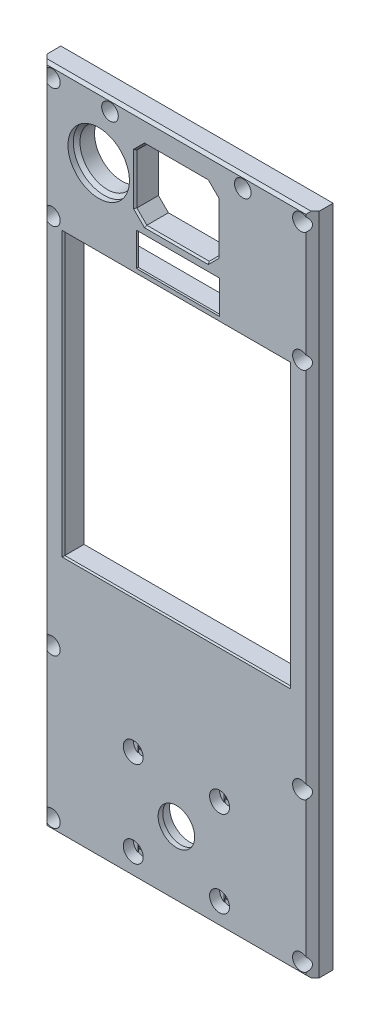
SolidWorks part; units mm, degrees
ref_plane "Front Plane" through (0, 0, 0) normal (0, 0, 1) x (1, 0, 0)
ref_plane "Top Plane" through (0, 0, 0) normal (0, 1, 0) x (1, 0, 0)
ref_plane "Right Plane" through (0, 0, 0) normal (1, 0, 0) x (0, 0, -1)
sketch "Sketch1" plane through (0, 0, 0) normal (0, 0, 1) x (1, 0, 0)
  line L1 (-41, -100) -> (41, -100)
  line L2 (-41, -100) -> (-41, 100)
  line L3 (-41, 100) -> (41, 100)
  line L4 (41, -100) -> (41, 100)
  line L5 (-41, -100) -> (41, 100) construction
  line L6 (-41, 100) -> (41, -100) construction
  line L7 (-34, -93) -> (34, -93)
  line L8 (-34, -93) -> (-34, 93)
  line L9 (-34, 93) -> (34, 93)
  line L10 (34, -93) -> (34, 93)
  line L11 (-34, -93) -> (34, 93) construction
  line L12 (-34, 93) -> (34, -93) construction
  point P0 (0, 0)
  point P6 (0, 0)
  dimension "D1" = 200
  dimension "D2" = 82
  dimension "D3" = 7
  dimension "D4" = 7
extrude "Boss-Extrude1" add sketch "Sketch1" along normal blind 7
sketch "Sketch2" plane through (0, 0, 7) normal (0, 0, 1) x (1, 0, 0)
  line L0 (34, -93) -> (34, 93) construction
  line L1 (-34, -93) -> (34, -93)
  line L2 (-34, -93) -> (-34, -57)
  line L3 (-34, -57) -> (34, -57)
  line L4 (34, -93) -> (34, -57)
  dimension "D1" = 36
extrude "Boss-Extrude2" add sketch "Sketch2" against normal up to surface (7 mm away) up to face at (0, 0, 0)
sketch "Sketch3" plane through (0, 0, 0) normal (0, 0, -1) x (-1, 0, 0)
  line L0 (0, -100) -> (0, -80) construction
  line L1 (41, -100) -> (-41, -100) construction
  circle A0 centre (0, -80) radius 5.5
  dimension "D1" = 11
  dimension "D2" = 20
extrude "Cut-Extrude1" cut sketch "Sketch3" against normal through all
sketch "Sketch4" plane through (0, 0, 0) normal (0, 0, -1) x (-1, 0, 0)
  circle A0 centre (0, -80) radius 6.05
  dimension "D1" = 12.1
extrude "Cut-Extrude2" cut sketch "Sketch4" against normal offset from surface (5.6 mm away) 1.4 up to face at (-5.5, -80, 7)
sketch "Sketch5" plane through (0, 0, 0) normal (0, 0, -1) x (-1, 0, 0)
  circle A0 centre (0, -80) radius 11.1
  dimension "D1" = 22.2
extrude "Cut-Extrude3" cut sketch "Sketch5" against normal offset from surface (3 mm away) 2.6 up to face at (-6.05, -80, 5.6)
sketch "Sketch6" plane through (0, 0, 0) normal (0, 0, -1) x (-1, 0, 0)
  line L1 (-13, -93) -> (13, -93) construction
  line L2 (-13, -93) -> (-13, -67) construction
  line L3 (-13, -67) -> (13, -67) construction
  line L4 (13, -93) -> (13, -67) construction
  line L5 (-13, -93) -> (13, -67) construction
  line L6 (-13, -67) -> (13, -93) construction
  circle A0 centre (-13, -67) radius 1.6
  circle A1 centre (13, -67) radius 1.6
  circle A2 centre (13, -93) radius 1.6
  circle A3 centre (-13, -93) radius 1.6
  point P0 (0, -80)
  dimension "D2" = 3.2
  dimension "D1" = 26
extrude "Cut-Extrude4" cut sketch "Sketch6" against normal through all
sketch "Sketch7" plane through (0, 0, 0) normal (0, 0, -1) x (-1, 0, 0)
  line L1 (-25, -99) -> (25, -99)
  line L2 (-25, -99) -> (-25, -61)
  line L3 (-25, -61) -> (25, -61)
  line L4 (25, -99) -> (25, -61)
  line L5 (-25, -99) -> (25, -61) construction
  line L6 (-25, -61) -> (25, -99) construction
  point P0 (0, -80)
  dimension "D1" = 50
  dimension "D2" = 38
extrude "Cut-Extrude5" cut sketch "Sketch7" against normal blind 1
sketch "Sketch8" plane through (0, 0, 7) normal (0, 0, 1) x (1, 0, 0)
  circle A0 centre (-13, -67) radius 3
  circle A1 centre (13, -67) radius 3
  circle A2 centre (13, -93) radius 3
  circle A3 centre (-13, -93) radius 3
  dimension "D1" = 6
extrude "Cut-Extrude6" cut sketch "Sketch8" against normal blind 3
sketch "Sketch9" plane through (0, 0, 7) normal (0, 0, 1) x (1, 0, 0)
  line L0 (-41, 100) -> (-41, -100) construction
  line L1 (-37.5, -96.5) -> (37.5, -96.5) construction
  line L2 (-37.5, -96.5) -> (-37.5, 96.5) construction
  line L3 (-37.5, 96.5) -> (37.5, 96.5) construction
  line L4 (37.5, -96.5) -> (37.5, 96.5) construction
  line L5 (-37.5, -96.5) -> (37.5, 96.5) construction
  line L6 (-37.5, 96.5) -> (37.5, -96.5) construction
  line L7 (41, 100) -> (-41, 100) construction
  circle A0 centre (-37.5, 96.5) radius 1.35
  circle A1 centre (37.5, 96.5) radius 1.35
  circle A2 centre (37.5, -96.5) radius 1.35
  circle A3 centre (-37.5, -96.5) radius 1.35
  circle A6 centre (-37.5, 60.5) radius 1.35
  circle A7 centre (-37.5, -51.5) radius 1.35
  circle A8 centre (37.5, -51.5) radius 1.35
  circle A9 centre (37.5, 60.5) radius 1.35
  point P0 (0, 0)
  dimension "D3" = 2.7
  dimension "D4" = 45
  dimension "D5" = 36
  dimension "D1" = 3.5
  dimension "D2" = 3.5
extrude "Cut-Extrude7" cut sketch "Sketch9" against normal through all
sketch "Sketch10" plane through (0, 0, 7) normal (0, 0, 1) x (1, 0, 0)
  circle A0 centre (-37.5, 96.5) radius 2.5
  circle A1 centre (37.5, 96.5) radius 2.5
  circle A2 centre (-37.5, 60.5) radius 2.5
  circle A3 centre (-37.5, -51.5) radius 2.5
  circle A4 centre (-37.5, -96.5) radius 2.5
  circle A5 centre (37.5, -96.5) radius 2.5
  circle A6 centre (37.5, 60.5) radius 2.5
  circle A7 centre (37.5, -51.5) radius 2.5
  dimension "D1" = 5
extrude "Cut-Extrude8" cut sketch "Sketch10" against normal blind 5
chamfer "Chamfer1" distance 2 angle 45 2 edges at (-41, 0, 7) (41, 0, 7)
sketch "Sketch11" plane through (0, 0, 7) normal (0, 0, 1) x (1, 0, 0)
  line L0 (34, -57) -> (34, 93) construction
  line L1 (-34, -57) -> (34, -57)
  line L2 (-34, -57) -> (-34, -26.5)
  line L3 (-34, -26.5) -> (34, -26.5)
  line L4 (34, -57) -> (34, -26.5)
  line L5 (-39, -100) -> (39, -100) construction
  dimension "D1" = 73.5
extrude "Boss-Extrude3" add sketch "Sketch11" against normal up to surface (7 mm away) up to face at (38.85, 96.5, 0)
sketch "Sketch12" plane through (0, 0, 2) normal (0, 0, 1) x (1, 0, 0)
  line L2 (-38.85, -98.6042) -> (-38.85, -94.3958)
  line L4 (-36.15, -98.6042) -> (-36.15, -94.3958)
  line L5 (-38.85, -98.6042) -> (-36.15, -94.3958) construction
  line L6 (-38.85, -94.3958) -> (-36.15, -98.6042) construction
  line L8 (-38.85, -53.6042) -> (-38.85, -49.3958)
  line L10 (-36.15, -53.6042) -> (-36.15, -49.3958)
  line L11 (-38.85, -53.6042) -> (-36.15, -49.3958) construction
  line L12 (-38.85, -49.3958) -> (-36.15, -53.6042) construction
  line L14 (-38.85, 58.3958) -> (-38.85, 62.6042)
  line L16 (-36.15, 58.3958) -> (-36.15, 62.6042)
  line L17 (-38.85, 58.3958) -> (-36.15, 62.6042) construction
  line L18 (-38.85, 62.6042) -> (-36.15, 58.3958) construction
  line L20 (-38.85, 94.3958) -> (-38.85, 98.6042)
  line L22 (-36.15, 94.3958) -> (-36.15, 98.6042)
  line L23 (-38.85, 94.3958) -> (-36.15, 98.6042) construction
  line L24 (-38.85, 98.6042) -> (-36.15, 94.3958) construction
  arc A0 (-39, -98.5) -> (-39, -94.5) centre (-37.5, -96.5) ccw construction
  circle A1 centre (-37.5, -51.5) radius 2.5 construction
  circle A2 centre (-37.5, 60.5) radius 2.5 construction
  arc A3 (-39, 94.5) -> (-39, 98.5) centre (-37.5, 96.5) ccw construction
  circle A4 centre (-37.5, 96.5) radius 1.35 construction
  circle A5 centre (-37.5, 96.5) radius 2.5 construction
  arc A6 (-36.15, 98.6042) -> (-38.85, 98.6042) centre (-37.5, 96.5) ccw
  arc A7 (-38.85, 94.3958) -> (-36.15, 94.3958) centre (-37.5, 96.5) ccw
  circle A8 centre (-37.5, 60.5) radius 1.35 construction
  arc A9 (-38.85, 58.3958) -> (-36.15, 58.3958) centre (-37.5, 60.5) ccw
  arc A10 (-36.15, 62.6042) -> (-38.85, 62.6042) centre (-37.5, 60.5) ccw
  circle A11 centre (-37.5, -51.5) radius 1.35 construction
  arc A12 (-38.85, -53.6042) -> (-36.15, -53.6042) centre (-37.5, -51.5) ccw
  arc A13 (-36.15, -49.3958) -> (-38.85, -49.3958) centre (-37.5, -51.5) ccw
  circle A14 centre (-37.5, -96.5) radius 1.35 construction
  arc A16 (-38.85, -98.6042) -> (-36.15, -98.6042) centre (-37.5, -96.5) ccw
  arc A18 (-36.15, -94.3958) -> (-38.85, -94.3958) centre (-37.5, -96.5) ccw
  point P0 (-37.5, -96.5)
  point P9 (-37.5, -51.5)
  point P17 (-37.5, 60.5)
  point P25 (-37.5, 96.5)
extrude "Cut-Extrude9" cut sketch "Sketch12" against normal blind 0.2
sketch "Sketch13" plane through (0, 0, 1.8) normal (0, 0, 1) x (1, 0, 0)
  line L0 (-36.15, -96.5) -> (-36.15, -94.3958) construction
  line L1 (-38.85, -97.85) -> (-36.15, -97.85)
  line L2 (-38.85, -97.85) -> (-38.85, -95.15)
  line L3 (-38.85, -95.15) -> (-36.15, -95.15)
  line L4 (-36.15, -97.85) -> (-36.15, -95.15)
  line L5 (-38.85, -97.85) -> (-36.15, -95.15) construction
  line L6 (-38.85, -95.15) -> (-36.15, -97.85) construction
  line L7 (-36.15, -51.5) -> (-36.15, -49.3958) construction
  line L8 (-38.85, -52.85) -> (-36.15, -52.85)
  line L9 (-38.85, -52.85) -> (-38.85, -50.15)
  line L10 (-38.85, -50.15) -> (-36.15, -50.15)
  line L11 (-36.15, -52.85) -> (-36.15, -50.15)
  line L12 (-38.85, -52.85) -> (-36.15, -50.15) construction
  line L13 (-38.85, -50.15) -> (-36.15, -52.85) construction
  line L14 (-36.15, 58.3958) -> (-36.15, 62.6042) construction
  line L15 (-38.85, 59.15) -> (-36.15, 59.15)
  line L16 (-38.85, 59.15) -> (-38.85, 61.85)
  line L17 (-38.85, 61.85) -> (-36.15, 61.85)
  line L18 (-36.15, 59.15) -> (-36.15, 61.85)
  line L19 (-38.85, 59.15) -> (-36.15, 61.85) construction
  line L20 (-38.85, 61.85) -> (-36.15, 59.15) construction
  line L21 (-36.15, 94.3958) -> (-36.15, 98.6042) construction
  line L22 (-38.85, 95.15) -> (-36.15, 95.15)
  line L23 (-38.85, 95.15) -> (-38.85, 97.85)
  line L24 (-38.85, 97.85) -> (-36.15, 97.85)
  line L25 (-36.15, 95.15) -> (-36.15, 97.85)
  line L26 (-38.85, 95.15) -> (-36.15, 97.85) construction
  line L27 (-38.85, 97.85) -> (-36.15, 95.15) construction
  arc A0 (-36.15, -96.5) -> (-38.85, -96.5) centre (-37.5, -96.5) ccw construction
  arc A1 (-36.15, -51.5) -> (-38.85, -51.5) centre (-37.5, -51.5) ccw construction
  arc A2 (-36.15, 60.5) -> (-38.85, 60.5) centre (-37.5, 60.5) ccw construction
  arc A3 (-36.15, 96.5) -> (-38.85, 96.5) centre (-37.5, 96.5) ccw construction
  point P0 (-37.5, -96.5)
  point P11 (-37.5, -51.5)
  point P22 (-37.5, 60.5)
  point P33 (-37.5, 96.5)
extrude "Cut-Extrude10" cut sketch "Sketch13" against normal blind 0.2
sketch "Sketch14" plane through (0, 0, 4) normal (0, 0, 1) x (1, 0, 0)
  line L2 (-14.6, -69.5377) -> (-14.6, -64.4623)
  line L4 (-11.4, -69.5377) -> (-11.4, -64.4623)
  line L5 (-14.6, -69.5377) -> (-11.4, -64.4623) construction
  line L6 (-14.6, -64.4623) -> (-11.4, -69.5377) construction
  line L8 (-14.6, -95.5377) -> (-14.6, -90.4623)
  line L10 (-11.4, -95.5377) -> (-11.4, -90.4623)
  line L11 (-14.6, -95.5377) -> (-11.4, -90.4623) construction
  line L12 (-14.6, -90.4623) -> (-11.4, -95.5377) construction
  circle A0 centre (-13, -67) radius 3 construction
  circle A1 centre (-13, -93) radius 3 construction
  circle A2 centre (-13, -67) radius 3 construction
  arc A3 (-14.6, -69.5377) -> (-11.4, -69.5377) centre (-13, -67) ccw
  arc A4 (-14.6, -95.5377) -> (-11.4, -95.5377) centre (-13, -93) ccw
  circle A5 centre (-13, -67) radius 1.6 construction
  circle A6 centre (-13, -93) radius 1.6 construction
  arc A7 (-11.4, -64.4623) -> (-14.6, -64.4623) centre (-13, -67) ccw
  arc A8 (-11.4, -90.4623) -> (-14.6, -90.4623) centre (-13, -93) ccw
  point P0 (-13, -67)
  point P8 (-13, -93)
extrude "Cut-Extrude11" cut sketch "Sketch14" against normal blind 0.2
sketch "Sketch15" plane through (0, 0, 3.8) normal (0, 0, 1) x (1, 0, 0)
  line L0 (-11.4, -67) -> (-11.4, -64.4623) construction
  line L1 (-14.6, -68.6) -> (-11.4, -68.6)
  line L2 (-14.6, -68.6) -> (-14.6, -65.4)
  line L3 (-14.6, -65.4) -> (-11.4, -65.4)
  line L4 (-11.4, -68.6) -> (-11.4, -65.4)
  line L5 (-14.6, -68.6) -> (-11.4, -65.4) construction
  line L6 (-14.6, -65.4) -> (-11.4, -68.6) construction
  line L7 (-11.4, -93) -> (-11.4, -90.4623) construction
  line L8 (-14.6, -94.6) -> (-11.4, -94.6)
  line L9 (-14.6, -94.6) -> (-14.6, -91.4)
  line L10 (-14.6, -91.4) -> (-11.4, -91.4)
  line L11 (-11.4, -94.6) -> (-11.4, -91.4)
  line L12 (-14.6, -94.6) -> (-11.4, -91.4) construction
  line L13 (-14.6, -91.4) -> (-11.4, -94.6) construction
  arc A0 (-11.4, -93) -> (-14.6, -93) centre (-13, -93) ccw construction
  arc A1 (-14.6, -67) -> (-11.4, -67) centre (-13, -67) ccw construction
  point P0 (-13, -67)
  point P8 (-13, -93)
extrude "Cut-Extrude12" cut sketch "Sketch15" against normal blind 0.2
mirror "Mirror1" about plane through (0, 0, 0) normal (1, 0, 0) of "Cut-Extrude10", "Cut-Extrude11", "Cut-Extrude12", "Cut-Extrude9"
chamfer "Chamfer2" distance 0.4 angle 45 4 edges at (34, 33.25, 7) (0, 93, 7) (0, -26.5, 7) (-34, 33.25, 7)
chamfer "Chamfer3" distance 0.8 angle 45 4 edges at (-41, 0, 0) (41, 0, 0) (0, -100, 7) (0, 100, 7)
sketch "Sketch17" plane through (0, 0, 0) normal (0, 0, -1) x (-1, 0, 0)
  line L0 (-20, 96.5) -> (20, 96.5) construction
  line L1 (-40.2, 100) -> (40.2, 100) construction
  circle A0 centre (-37.5, 96.5) radius 1.35 construction
  circle A1 centre (-37.5, 96.5) radius 1.35 construction
  circle A2 centre (-20, 96.5) radius 1.35
  circle A3 centre (20, 96.5) radius 1.35
  point P3 (0, 96.5)
  point P6 (0, 100)
  dimension "D1" = 40
extrude "Cut-Extrude13" cut sketch "Sketch17" against normal through all
sketch "Sketch18" plane through (0, 0, 7) normal (0, 0, 1) x (1, 0, 0)
  circle A0 centre (-20, 96.5) radius 2.5
  circle A1 centre (20, 96.5) radius 2.5
  arc A2 (-39, 94.5) -> (-39, 98.5) centre (-37.5, 96.5) ccw construction
extrude "Cut-Extrude14" cut sketch "Sketch18" against normal up to surface (5 mm away) up to face at (35.575, 96.5, 2)
sketch "Sketch19" plane through (0, 0, 2) normal (0, 0, 1) x (1, 0, 0)
  line L2 (-21.35, 94.3958) -> (-21.35, 98.6042)
  line L4 (-18.65, 94.3958) -> (-18.65, 98.6042)
  line L5 (-21.35, 94.3958) -> (-18.65, 98.6042) construction
  line L6 (-21.35, 98.6042) -> (-18.65, 94.3958) construction
  line L8 (18.65, 94.3958) -> (18.65, 98.6042)
  line L10 (21.35, 94.3958) -> (21.35, 98.6042)
  line L11 (18.65, 94.3958) -> (21.35, 98.6042) construction
  line L12 (18.65, 98.6042) -> (21.35, 94.3958) construction
  circle A0 centre (-20, 96.5) radius 2.5 construction
  circle A1 centre (20, 96.5) radius 2.5 construction
  circle A2 centre (20, 96.5) radius 1.35 construction
  circle A3 centre (-20, 96.5) radius 1.35 construction
  circle A4 centre (-20, 96.5) radius 2.5 construction
  arc A5 (18.65, 94.3958) -> (21.35, 94.3958) centre (20, 96.5) ccw
  arc A6 (-18.65, 98.6042) -> (-21.35, 98.6042) centre (-20, 96.5) ccw
  arc A7 (21.35, 98.6042) -> (18.65, 98.6042) centre (20, 96.5) ccw
  arc A8 (-21.35, 94.3958) -> (-18.65, 94.3958) centre (-20, 96.5) ccw
  point P0 (-20, 96.5)
  point P8 (20, 96.5)
extrude "Cut-Extrude15" cut sketch "Sketch19" against normal blind 0.2
sketch "Sketch20" plane through (0, 0, 1.8) normal (0, 0, 1) x (1, 0, 0)
  line L0 (-18.65, 94.3958) -> (-18.65, 98.6042) construction
  line L1 (-21.35, 95.15) -> (-18.65, 95.15)
  line L2 (-21.35, 95.15) -> (-21.35, 97.85)
  line L3 (-21.35, 97.85) -> (-18.65, 97.85)
  line L4 (-18.65, 95.15) -> (-18.65, 97.85)
  line L5 (-21.35, 95.15) -> (-18.65, 97.85) construction
  line L6 (-21.35, 97.85) -> (-18.65, 95.15) construction
  line L7 (21.35, 96.5) -> (21.35, 98.6042) construction
  line L8 (18.65, 95.15) -> (21.35, 95.15)
  line L9 (18.65, 95.15) -> (18.65, 97.85)
  line L10 (18.65, 97.85) -> (21.35, 97.85)
  line L11 (21.35, 95.15) -> (21.35, 97.85)
  line L12 (18.65, 95.15) -> (21.35, 97.85) construction
  line L13 (18.65, 97.85) -> (21.35, 95.15) construction
  arc A0 (18.65, 96.5) -> (21.35, 96.5) centre (20, 96.5) ccw construction
  point P0 (-20, 96.5)
  point P8 (20, 96.5)
extrude "Cut-Extrude16" cut sketch "Sketch20" against normal blind 0.2
sketch "Skizze6" plane through (0, 0, 7) normal (0, 0, 1) x (1, 0, 0)
  line L0 (12.4, 93.4) -> (34.4, 71.4) construction
  line L1 (34.4, 93.4) -> (12.4, 93.4)
  line L2 (34.4, 93.4) -> (34.4, 71.4)
  line L3 (34.4, 71.4) -> (12.4, 71.4)
  line L4 (12.4, 93.4) -> (12.4, 71.4)
  line L5 (23.4, 93.4) -> (23.4, 71.4) construction
  circle A0 centre (23.4, 81.4) radius 8.25
  point P10 (23.4, 82.4)
  dimension "D1" = 16.5
  dimension "D2" = 22
  dimension "D3" = 22
  dimension "D4" = 1
extrude "Aufsatz-Linear austragen1" add sketch "Skizze6" against normal up to surface (7 mm away) up to face at (18.65, 96.5, 0)
sketch "Skizze7" plane through (0, 0, 7) normal (0, 0, 1) x (1, 0, 0)
  circle A0 centre (23.4, 81.4) radius 9.25
  dimension "D1" = 18.5
extrude "Schnitt-Linear austragen2" cut sketch "Skizze7" against normal blind 1.6
chamfer "Fase6" distance 0.5 angle 45 2 edges at (12.4, 82.4, 7) (23.4, 71.4, 7)
chamfer "Fase7" distance 4 angle 45 1 edges at (12.4, 71.4, 3.25)
chamfer "Fase8" distance 1 angle 45 1 edges at (31.65, 81.4, 5.4)
mirror "Mirror2" about plane through (0, 0, 0) normal (1, 0, 0) of "Fase6", "Schnitt-Linear austragen2", "Fase8", "Aufsatz-Linear austragen1", "Fase7"
sketch "Sketch21" plane through (0, 0, 7) normal (0, 0, 1) x (1, 0, 0)
  line L0 (34.4, 71.9) -> (34.4, -26.9) construction
  line L1 (-34.4, 71.9) -> (-15.9, 71.9)
  line L2 (-34.4, 71.9) -> (-34.4, 57.9)
  line L3 (-34.4, 57.9) -> (34.4, 57.9)
  line L4 (34.4, 71.9) -> (34.4, 57.9)
  line L5 (-15.9, 71.9) -> (-12.4, 75.4)
  line L6 (-12.4, 75.4) -> (-12.4, 71.9)
  line L7 (12.4, 75.4) -> (15.9, 71.9)
  line L8 (12.4, 75.4) -> (12.4, 71.9)
  line L9 (-12.4, 71.9) -> (12.4, 71.9)
  line L10 (15.9, 71.9) -> (34.4, 71.9)
  dimension "D1" = 14
extrude "Boss-Extrude5" add sketch "Sketch21" against normal up to surface (7 mm away) up to face at (0, 56.94, 0)
chamfer "Chamfer4" distance 0.5 angle 45 3 edges at (12.4, 73.65, 7) (-12.4, 73.65, 7) (0, 71.9, 7)
sketch "Sketch22" plane through (0, 0, 0) normal (0, 0, -1) x (-1, 0, 0)
  line L0 (0, 71.9) -> (0, 57.9) construction
  line L1 (-12.4, 71.9) -> (12.4, 71.9) construction
  line L2 (34, 57.9) -> (-34, 57.9) construction
  line L4 (-18.95, 58.75) -> (18.95, 58.75)
  line L5 (-18.95, 58.75) -> (-18.95, 71.05)
  line L6 (-18.95, 71.05) -> (18.95, 71.05)
  line L7 (18.95, 58.75) -> (18.95, 71.05)
  line L8 (-18.95, 58.75) -> (18.95, 71.05) construction
  line L9 (-18.95, 71.05) -> (18.95, 58.75) construction
  point P6 (0, 64.9)
  dimension "D1" = 37.9
  dimension "D2" = 12.3
extrude "Cut-Extrude17" cut sketch "Sketch22" against normal offset from surface (6.4 mm away) 0.6 up to face at (0, 15.5, 7)
sketch "Sketch23" plane through (0, 0, 6.4) normal (0, 0, -1) x (-1, 0, 0)
  line L0 (-18.95, 71.05) -> (-18.95, 58.75) construction
  line L1 (-12.95, 59.55) -> (12.05, 59.55)
  line L2 (-12.95, 59.55) -> (-12.95, 69.55)
  line L3 (-12.95, 69.55) -> (12.05, 69.55)
  line L4 (12.05, 59.55) -> (12.05, 69.55)
  line L5 (-12.95, 59.55) -> (12.05, 69.55) construction
  line L6 (-12.95, 69.55) -> (12.05, 59.55) construction
  line L7 (-18.95, 71.05) -> (18.95, 71.05) construction
  point P0 (-0.45, 64.55)
  dimension "D1" = 25
  dimension "D2" = 10
  dimension "D3" = 6
  dimension "D4" = 1.5
extrude "Cut-Extrude18" cut sketch "Sketch23" against normal through all
chamfer "Chamfer5" distance 0.4 angle 45 1 edges at (0, 57.9, 7)
sketch "Sketch24" plane through (0, 0, 7) normal (0, 0, 1) x (1, 0, 0)
  line L1 (-12.9, 93.4) -> (12.9, 93.4)
  line L2 (-12.9, 93.4) -> (-12.9, 71.4)
  line L3 (-12.9, 71.4) -> (12.9, 71.4)
  line L4 (12.9, 93.4) -> (12.9, 71.4)
  line L5 (-12.4, 93) -> (12.4, 93)
  line L6 (-12.4, 93) -> (-12.4, 71.9)
  line L7 (-12.4, 71.9) -> (12.4, 71.9)
  line L8 (12.4, 93) -> (12.4, 71.9)
extrude "Boss-Extrude6" add sketch "Sketch24" against normal up to vertex (0.5 mm away) up to point (12.4, 71.9, 6.5)
chamfer "Chamfer7" distance 3 angle 45 4 edges at (12.4, 71.9, 3.5) (12.4, 93, 3.5) (-12.4, 93, 3.5) (-12.4, 71.9, 3.5)
chamfer "Chamfer8" distance 0.5 angle 45 8 edges at (-10.9, 73.4, 7) (0, 71.9, 7) (10.9, 73.4, 7) (12.4, 82.45, 7) (10.9, 91.5, 7) (0, 93, 7) (-10.9, 91.5, 7) (-12.4, 82.45, 7)
chamfer "Chamfer9" distance 0.8 angle 45 6 edges at (-34, 15.7, 0) (0, 57.9, 0) (34, 15.7, 0) (0, -26.5, 0) (0, -100, 0) (0, 100, 0)
sketch "Sketch28" plane through (0, 0, 7) normal (0, 0, 1) x (1, 0, 0)
  circle A0 centre (23.4, 81.4) radius 10
  dimension "D1" = 20
extrude "Boss-Extrude8" add sketch "Sketch28" against normal up to surface (7 mm away) up to face at (0, 15.7, 0)
